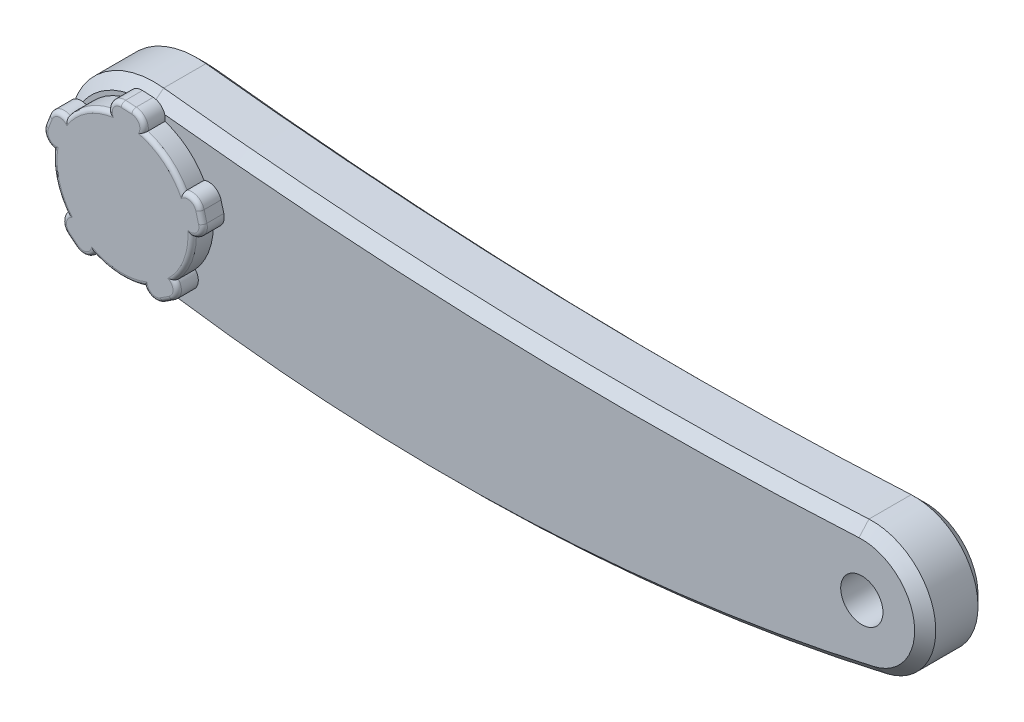
SolidWorks part; units mm, degrees
ref_plane "Ön Düzlem" through (0, 0, 0) normal (0, 0, 1) x (1, 0, 0)
ref_plane "Üst Düzlem" through (0, 0, 0) normal (0, 1, 0) x (1, 0, 0)
ref_plane "Sağ Düzlem" through (0, 0, 0) normal (1, 0, 0) x (0, 0, -1)
sketch "Çizim1" plane through (0, 0, 0) normal (0, 0, 1) x (1, 0, 0)
  line L0 (85, 0) -> (-85, 0) construction
  circle A0 centre (-85, 0) radius 20
  circle A1 centre (85, 0) radius 15
  arc A2 (-82.7465, 19.8726) -> (84.1861, 14.9779) centre (29.9265, 1013.5048) ccw
  arc A3 (-88.3618, -19.7154) -> (88.3697, -14.6166) centre (-12.7206, 423.8817) ccw
  point P4 (0, 0)
  dimension "D2" = 40
  dimension "D3" = 30
  dimension "D4" = 450
  dimension "D5" = 1000
  dimension "D1" = 170
extrude "Yükseklik-Ekstrüzyon1" add sketch "Çizim1" along normal mid plane 15 contours A0 | L0 A1 A2 A0 | A1 L0 A0 A3 | A1 region at (-0.4487, -12.3679, 0) region at (-1.0237, 7.6812, 0) region at (74.4175, 10.0231, 0) region at (-72.4659, -14.8523, 0)
chamfer "Pah1" distance 2.5 angle 45 8 edges at (0.2568, -25.9311, -7.5) (-104.8018, 2.8087, -7.5) (99.8523, 2.0996, -7.5) (0.6174, 13.9344, -7.5) (0.2568, -25.9311, 7.5) (-104.8018, 2.8087, 7.5) (99.8523, 2.0996, 7.5) (0.6174, 13.9344, 7.5)
sketch "Çizim2" plane through (0, 0, 7.5) normal (0, 0, 1) x (1, 0, 0)
  circle A1 centre (-85, 0) radius 16.5
  dimension "D1" = 33
extrude "Yükseklik-Ekstrüzyon2" add sketch "Çizim2" along normal blind 5
sketch "Çizim3" plane through (0, 0, 12.5) normal (0, 0, 1) x (1, 0, 0)
  line L0 (-85, 0) -> (-68.9097, 0)
  line L2 (-66.0119, 3.7765) -> (-66.6676, 6.2235)
  line L3 (-71.0654, 8.0452) -> (-85, 0)
  line L4 (-85, 0) -> (-66.3397, 5) construction
  line L5 (-85, 0) -> (-80.0278, -15.3028)
  line L6 (-73.0426, -10.7665) -> (-85, 0)
  line L7 (-75.5407, -16.8918) -> (-73.416, -15.512)
  line L8 (-85, 0) -> (-98.0173, -9.4577)
  line L9 (-91.5445, -14.6992) -> (-85, 0)
  line L10 (-98.142, -14.2161) -> (-96.1731, -15.8105)
  line L11 (-85, 0) -> (-98.0173, 9.4577)
  line L12 (-101.0022, 1.6819) -> (-85, 0)
  line L13 (-102.5814, 8.1057) -> (-103.4893, 5.7406)
  line L14 (-85, 0) -> (-80.0278, 15.3028)
  line L15 (-88.3454, 15.7387) -> (-85, 0)
  line L16 (-82.724, 19.2257) -> (-85.2539, 19.3583)
  arc A0 (-73.0426, -10.7665) -> (-73.416, -15.512) centre (-75.05, -12.996) cw
  arc A1 (-66.0119, 3.7765) -> (-68.9097, 0) centre (-68.9097, 3) cw
  arc A2 (-71.0654, 8.0452) -> (-66.6676, 6.2235) centre (-69.5654, 5.4471) cw
  arc A3 (-75.5407, -16.8918) -> (-80.0278, -15.3028) centre (-77.1746, -14.3758) cw
  arc A4 (-91.5445, -14.6992) -> (-96.1731, -15.8105) centre (-94.2852, -13.479) cw
  arc A5 (-98.142, -14.2161) -> (-98.0173, -9.4577) centre (-96.254, -11.8847) cw
  arc A6 (-101.0022, 1.6819) -> (-103.4893, 5.7406) centre (-100.6886, 4.6655) cw
  arc A7 (-102.5814, 8.1057) -> (-98.0173, 9.4577) centre (-99.7807, 7.0306) cw
  arc A8 (-88.3454, 15.7387) -> (-85.2539, 19.3583) centre (-85.4109, 16.3624) cw
  arc A9 (-82.724, 19.2257) -> (-80.0278, 15.3028) centre (-82.881, 16.2299) cw
  circle A10 centre (-85, 0) radius 2
  point P11 (-67.6795, 10)
  circle M29 centre (-85, 0) radius 16.5
  dimension "D3" = 3
  dimension "D5" = 4
  dimension "D1" = 30
  dimension "D2" = 20
  dimension "D4" = 5
extrude "Yükseklik-Ekstrüzyon3" add sketch "Çizim3" against normal blind 5 contours A9 L16 A8 M29 | L4 L2 A2 M29 | L4 A1 L2 M29 | A3 L7 A0 M29 | A5 L10 A4 M29 | A7 L13 A6 M29 | A10 L11 A7 A6 L12 M29 | A10 L14 A9 A8 L15 M29 | A10 L4 A2 L3 M29 | L4 A10 L0 A1 M29 | A10 L5 A3 A0 L6 M29 | A10 L8 A5 A4 L9 M29 region at (-73.9833, 1.4506, 12.5) region at (-74.734, 4.2521, 12.5) region at (-78.9998, -9.2394, 12.5) region at (-91.9331, -8.5616, 12.5) region at (-95.285, 3.9481, 12.5) region at (-84.4234, 11.0017, 12.5) region at (-68.4431, 6.4563, 12.5) region at (-67.4332, 2.6871, 12.5) region at (-75.3796, -14.8141, 12.5) region at (-96.1162, -13.7273, 12.5) region at (-101.4905, 6.3301, 12.5) region at (-84.0756, 17.6395, 12.5)
fillet "Radyus1" radius 1 20 edges at (-103.3478, 3.2767, 12.5) (-103.0354, 6.9231, 12.5) (-100.8276, 9.842, 12.5) (-93.9865, 13.8381, 12.5) (-87.5535, 18.4623, 12.5) (-83.9889, 19.292, 12.5) (-80.5307, 18.0943, 12.5) (-74.6162, 12.8229, 12.5) (-68.2303, 8.1337, 12.5) (-66.3397, 5, 12.5) (-66.4102, 1.3409, 12.5) (-69.5959, -5.9131, 12.5) (-72.0823, -13.4355, 12.5) (-74.4784, -16.2019, 12.5) (-77.9802, -17.2656, 12.5) (-85.8635, -16.4774, 12.5) (-93.7861, -16.4372, 12.5) (-97.1575, -15.0133, 12.5) (-99.2513, -12.0116, 12.5) (-100.9378, -4.2705, 12.5)
sketch "Çizim4" plane through (0, 0, 7.5) normal (0, 0, 1) x (1, 0, 0)
  circle A0 centre (85, 0) radius 5
  dimension "D1" = 10
extrude "Kes-Ekstrüzyon1" cut sketch "Çizim4" against normal blind 10
sketch "Çizim5" plane through (0, 0, -7.5) normal (0, 0, -1) x (-1, 0, 0)
  circle A0 centre (85, 0) radius 5
  dimension "D1" = 10
extrude "Yükseklik-Ekstrüzyon4" add sketch "Çizim5" along normal blind 10
